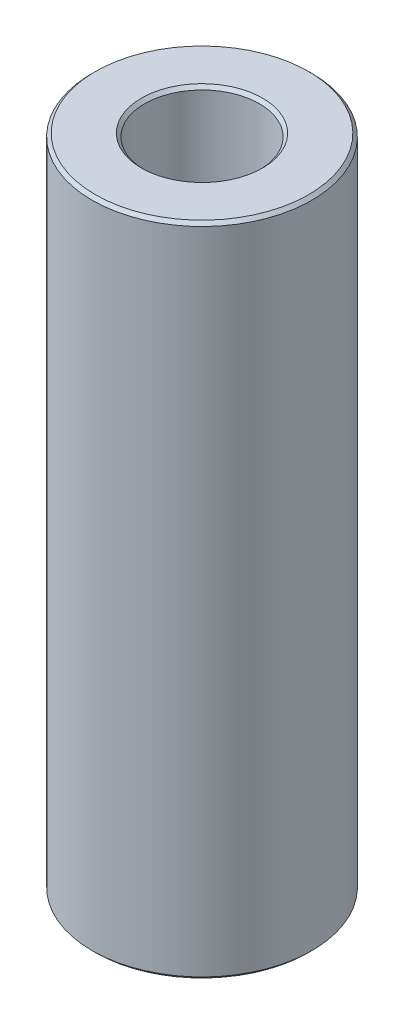
SolidWorks part; units mm, degrees
ref_plane "Front Plane" through (0, 0, 0) normal (0, 0, 1) x (1, 0, 0)
ref_plane "Top Plane" through (0, 0, 0) normal (0, 1, 0) x (1, 0, 0)
ref_plane "Right Plane" through (0, 0, 0) normal (1, 0, 0) x (0, 0, -1)
sketch "Sketch1" plane through (0, 0, 0) normal (0, 1, 0) x (1, 0, 0)
  circle A0 centre (0, 0) radius 37.5
  dimension "SLEEVE_OD" = 75
extrude "Boss-Extrude1" add sketch "Sketch1" along normal blind 223.9731
sketch "Sketch2" plane through (0, 0, 0) normal (0, 1, 0) x (1, 0, 0)
  circle A0 centre (0, 0) radius 19.577
  dimension "BORE_D" = 39.154
extrude "Cut-Extrude1" cut sketch "Sketch2" along normal through all
chamfer "Chamfer1" distance 1.0987 angle 45 4 edges at (0, 223.9731, 19.577) (0, 0, 19.577) (0, 0, 37.5) (0, 223.9731, 37.5)
